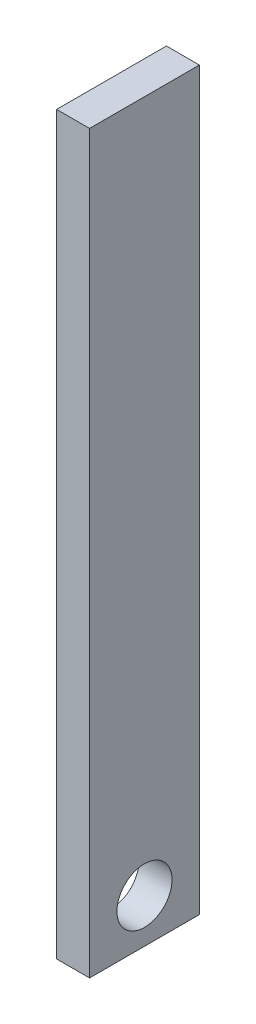
SolidWorks part; units mm, degrees
material "C-Glass Fiber"
ref_plane "xy_plane" through (0, 0, 0) normal (0, 0, 1) x (1, 0, 0)
ref_plane "zx_plane" through (0, 0, 0) normal (0, 1, 0) x (1, 0, 0)
ref_plane "yz_plane" through (0, 0, 0) normal (1, 0, 0) x (0, 0, -1)
ref_axis "x_axis" through (-80.9, 0, 0) along (1, 0, 0)
ref_axis "y_axis" through (0, -50, 0) along (0, 1, 0)
ref_axis "z_axis" through (0, 0, -80.9) along (0, 0, 1)
ref_plane "xMid_plane" through (0, 0, 0) normal (1, 0, 0) x (0, 0, -1)
ref_plane "xMin_plane" through (-1.5, 0, 0) normal (1, 0, 0) x (0, 0, -1)
ref_plane "xMax_plane" through (1.5, 0, 0) normal (1, 0, 0) x (0, 0, -1)
ref_plane "yMid_plane" through (0, 0, 0) normal (0, 1, 0) x (1, 0, 0)
ref_plane "yMin_plane" through (0, -33.5, 0) normal (0, 1, 0) x (1, 0, 0)
ref_plane "yMax_plane" through (0, 33.5, 0) normal (0, 1, 0) x (1, 0, 0)
ref_plane "zMid_plane" through (0, 0, 0) normal (0, 0, 1) x (1, 0, 0)
ref_plane "zMin_plane" through (0, 0, -5) normal (0, 0, 1) x (1, 0, 0)
ref_plane "zMax_plane" through (0, 0, 5) normal (0, 0, 1) x (1, 0, 0)
sketch "projectionXy_sketch" plane through (0, 0, 0) normal (0, 0, 1) x (1, 0, 0)
  line L0 (55, 33.5) -> (-55, 33.5) construction
  line L1 (-1.5, 33.5) -> (1.5, 33.5)
  line L2 (-1.5, 33.5) -> (-1.5, -33.5)
  line L3 (-1.5, -33.5) -> (1.5, -33.5)
  line L4 (1.5, 33.5) -> (1.5, -33.5)
  line L5 (55, -33.5) -> (-55, -33.5) construction
  line L6 (1.5, -55) -> (1.5, 55) construction
  line L7 (-1.5, -55) -> (-1.5, 55) construction
extrude "mainBody_extrude" add sketch "projectionXy_sketch" along normal up to surface (5 mm away) from surface up to plane "zMax_plane" starting at plane "zMin_plane"
sketch3d "pivotTargetRootPoint_sketch"
  point P0 (0, -29.5, 0)
  dimension "D1" = 4
ref_point "pivotTargetRootPoint"
ref_axis "pivotTarget_axis" through (0, -29.5, 0) along (1, 0, 0)
sketch "pivotShaftHole_sketch" plane through (0, 0, 0) normal (1, 0, 0) x (0, 0, -1)
  circle A0 centre (0, -29.5) radius 2.51
  dimension "D1" = 5.02
extrude "pivotShaftHole_cut" cut sketch "pivotShaftHole_sketch" against normal through all both and the other way through all from surface starting at plane "xMid_plane"
equation "\"D1@xMin_plane\" = \"externalParameters.this.extent.x\" / 2"
equation "\"D1@xMax_plane\" = \"externalParameters.this.extent.x\" / 2"
equation "\"D1@yMin_plane\" = \"externalParameters.this.extent.y\" / 2"
equation "\"D1@yMax_plane\" = \"externalParameters.this.extent.y\" / 2"
equation "\"D1@zMin_plane\"= \"externalParameters.this.extent.z\" / 2"
equation "\"D1@zMax_plane\" = \"externalParameters.this.extent.z\" / 2"
equation "\"D1@pivotTargetRootPoint_sketch\"=\"externalParameters.this.pivotDedendum\""
equation "\"D1@pivotShaftHole_sketch\"=\"externalParameters.pivotShaft.holeDiameter\""
